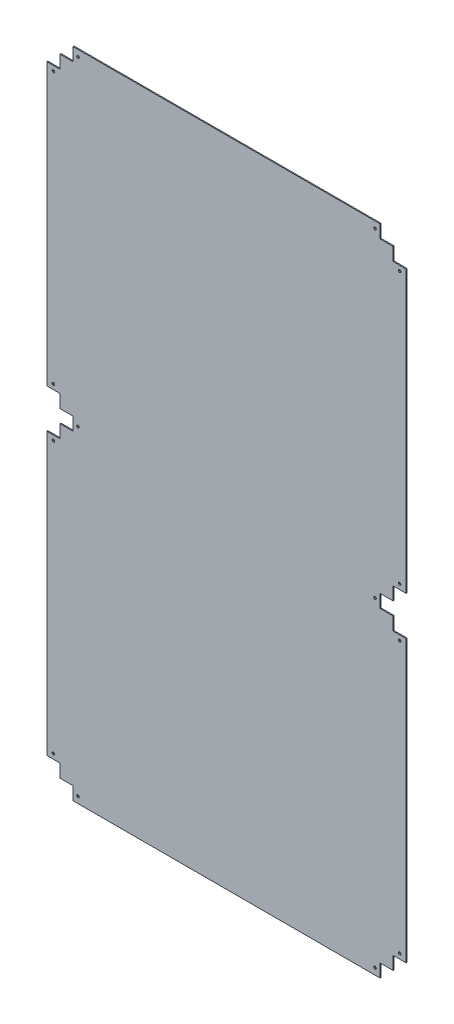
SolidWorks part; units mm, degrees
ref_plane "Piano frontale" through (0, 0, 0) normal (0, 0, 1) x (1, 0, 0)
ref_plane "Piano superiore" through (0, 0, 0) normal (0, 1, 0) x (1, 0, 0)
ref_plane "Piano destro" through (0, 0, 0) normal (1, 0, 0) x (0, 0, -1)
sketch "Schizzo1" plane through (0, 0, 0) normal (0, 0, 1) x (1, 0, 0)
  line L1 (-550, 1000) -> (550, 1000)
  line L2 (-550, 1000) -> (-550, -1000)
  line L3 (-550, -1000) -> (550, -1000)
  line L4 (550, 1000) -> (550, -1000)
  line L5 (-550, 1000) -> (550, -1000) construction
  line L6 (-550, -1000) -> (550, 1000) construction
  point P0 (0, 0)
  dimension "D1" = 2000
  dimension "D2" = 1100
base flange "Base-Flangia1" sketch "Schizzo1" thickness 3 reverse thickness direction no parameters "D1"=1
sketch "Schizzo2" plane through (0, 0, 0) normal (0, 0, 1) x (1, 0, 0)
  line L0 (-550, -1000) -> (-470, -1000)
  line L33 (-550, -1000) -> (550, -1000) construction
  line L34 (-470, -1000) -> (-470, -960)
  line L35 (-470, -960) -> (-510, -960)
  line L36 (-510, -960) -> (-510, -920)
  line L37 (-510, -920) -> (-550, -920)
  line L38 (-550, 1000) -> (-550, -1000) construction
  line L39 (-550, -920) -> (-550, -1000)
  line L40 (550, -1000) -> (470, -1000)
  line L41 (470, -1000) -> (470, -960)
  line L42 (470, -960) -> (510, -960)
  line L43 (510, -960) -> (510, -920)
  line L44 (510, -920) -> (550, -920)
  line L45 (550, 1000) -> (550, -1000) construction
  line L46 (550, -920) -> (550, -1000)
  line L47 (550, 1000) -> (470, 1000)
  line L48 (-550, 1000) -> (550, 1000) construction
  line L49 (470, 1000) -> (470, 960)
  line L50 (470, 960) -> (510, 960)
  line L51 (510, 960) -> (510, 920)
  line L52 (510, 920) -> (550, 920)
  line L53 (550, 920) -> (550, 1000)
  line L54 (-550, 1000) -> (-550, 920)
  line L55 (-550, 920) -> (-510, 920)
  line L56 (-510, 920) -> (-510, 960)
  line L57 (-510, 960) -> (-470, 960)
  line L58 (-470, 960) -> (-470, 1000)
  line L59 (-470, 1000) -> (-550, 1000)
  dimension "D1" = 80
  dimension "D2" = 80
  dimension "D3" = 40
  dimension "D4" = 40
  dimension "D5" = 40
  dimension "D6" = 80
  dimension "D7" = 80
  dimension "D8" = 40
  dimension "D9" = 40
  dimension "D10" = 40
  dimension "D11" = 80
  dimension "D12" = 80
  dimension "D13" = 80
  dimension "D14" = 80
  dimension "D15" = 40
  dimension "D16" = 40
extrude "Taglio-Estrusione1" cut sketch "Schizzo2" against normal through all normal cut yes
sketch "Schizzo4" plane through (0, 0, 0) normal (0, 0, 1) x (1, 0, 0)
  line L0 (-1000, 0) -> (49000, 0) construction
  line L1 (-550, -60) -> (-550, 60)
  line L2 (-550, 920) -> (-550, -920) construction
  line L3 (-550, 60) -> (-510, 60)
  line L4 (-510, 60) -> (-510, 20)
  line L5 (-510, 20) -> (-470, 20)
  line L6 (-470, 20) -> (-470, -20)
  line L7 (-510, -20) -> (-470, -20)
  line L8 (-510, -60) -> (-510, -20)
  line L9 (-550, -60) -> (-510, -60)
  line L10 (0, -1000) -> (0, 49000) construction
  line L11 (510, 20) -> (470, 20)
  line L12 (510, 60) -> (510, 20)
  line L13 (550, 60) -> (510, 60)
  line L14 (550, -60) -> (550, 60)
  line L15 (550, -60) -> (510, -60)
  line L16 (510, -60) -> (510, -20)
  line L17 (510, -20) -> (470, -20)
  line L18 (470, 20) -> (470, -20)
  point P12 (-470, 0)
  point P15 (-550, 0)
  dimension "D1" = 60
  dimension "D2" = 40
  dimension "D3" = 40
  dimension "D4" = 20
extrude "Taglio-Estrusione3" cut sketch "Schizzo4" against normal through all normal cut yes
sketch "Schizzo6" plane through (0, 0, -3) normal (0, 0, -1) x (-1, 0, 0)
  line L0 (0, -1000) -> (0, 49000) construction
  line L2 (470, 1000) -> (-470, 1000) construction
  line L4 (470, -20) -> (470, 20) construction
  line L6 (470, 20) -> (510, 20) construction
  line L7 (470, 960) -> (470, 1000) construction
  line L8 (550, 920) -> (550, 60) construction
  line L9 (550, 920) -> (510, 920) construction
  line L10 (550, -60) -> (510, -60) construction
  line L11 (550, -60) -> (550, -920) construction
  line L12 (510, 60) -> (550, 60) construction
  line L14 (510, -920) -> (550, -920) construction
  line L15 (470, -1000) -> (470, -960) construction
  line L16 (470, -1000) -> (-470, -1000) construction
  circle A1 centre (-454.75, -980) radius 4
  circle A2 centre (-530, -904.75) radius 4
  circle A3 centre (-530, -75.25) radius 4
  circle A4 centre (-454.75, 0) radius 4
  circle A5 centre (-530, 75.25) radius 4
  circle A6 centre (-530, 904.75) radius 4
  circle A7 centre (-454.75, 980) radius 4
  circle A56 centre (454.75, 980) radius 4
  circle A57 centre (530, 904.75) radius 4
  circle A58 centre (530, 75.25) radius 4
  circle A59 centre (454.75, 0) radius 4
  circle A60 centre (530, -75.25) radius 4
  circle A61 centre (530, -904.75) radius 4
  circle A62 centre (454.75, -980) radius 4
  dimension "D4" = 8
  dimension "D5" = 8
  dimension "D6" = 8
  dimension "D7" = 8
  dimension "D8" = 8
  dimension "D14" = 8
  dimension "D15" = 8
  dimension "D16" = 20
  dimension "D9" = 15.25
  dimension "D11" = 20
  dimension "D12" = 15.25
  dimension "D13" = 20
  dimension "D17" = 15.25
  dimension "D18" = 15.25
  dimension "D19" = 20
  dimension "D20" = 15.25
  dimension "D21" = 20
  dimension "D24" = 20
  dimension "D25" = 15.25
  dimension "D26" = 15.25
  dimension "D27" = 20
extrude "Taglio-Estrusione4" cut sketch "Schizzo6" against normal through all normal cut yes
sketch "Linee di piegatura1" [suppressed] plane through (0, 0, 0) normal (0, 1, 0) x (1, 0, 0)
sketch "Casella di contorno1" [suppressed] plane through (0, 0, 0) normal (0, 1, 0) x (1, 0, 0)
sheet metal parameters "Lamiera1" thickness 3 parameters "D1"=1
flat pattern "Ripetizione piatta1" [suppressed]
sketch "Linee di piegatura2" plane through (0, 0, 0) normal (0, 1, 0) x (1, 0, 0)
sketch3d "Casella di contorno2" [suppressed]
  line L0 (790, 1040, 0) -> (790, -1040, 0) construction
  line L1 (-790, 1040, 0) -> (-790, -1040, 0) construction
  line L2 (790, 1040, 0) -> (-790, 1040, 0) construction
  line L3 (790, -1040, 0) -> (-790, -1040, 0) construction
sheet metal parameters "Lamiera3" thickness 3 parameters "D1"=1
flat pattern "Ripetizione piatta1"
sketch "Linee di piegatura2" plane through (0, 0, 0) normal (0, 1, 0) x (1, 0, 0)
sketch3d "Casella di contorno2" [suppressed]
  line L0 (790, 1040, 0) -> (790, -1040, 0) construction
  line L1 (-790, 1040, 0) -> (-790, -1040, 0) construction
  line L2 (790, 1040, 0) -> (-790, 1040, 0) construction
  line L3 (790, -1040, 0) -> (-790, -1040, 0) construction
sheet metal parameters "Lamiera5" thickness 3 parameters "D1"=1
flat pattern "Ripetizione piatta1" [suppressed]
sketch "Linee di piegatura2" plane through (0, 0, 0) normal (0, 1, 0) x (1, 0, 0)
sketch3d "Casella di contorno2" [suppressed]
  line L0 (790, 1040, 0) -> (790, -1040, 0) construction
  line L1 (-790, 1040, 0) -> (-790, -1040, 0) construction
  line L2 (790, 1040, 0) -> (-790, 1040, 0) construction
  line L3 (790, -1040, 0) -> (-790, -1040, 0) construction
sketch "Schizzo3-1" [suppressed] plane through (0, 0, -3) normal (0, 0, -1) x (-1, 0, 0)
  arc A16 (774, -944.75) -> (766, -944.75) centre (770, -944.75) ccw
  arc A17 (766, -944.75) -> (774, -944.75) centre (770, -944.75) ccw
  arc A18 (694.75, -1024) -> (694.75, -1016) centre (694.75, -1020) ccw
  arc A19 (694.75, -1016) -> (694.75, -1024) centre (694.75, -1020) ccw
  arc A20 (-694.75, -1024) -> (-694.75, -1016) centre (-694.75, -1020) ccw
  arc A21 (-694.75, -1016) -> (-694.75, -1024) centre (-694.75, -1020) ccw
  arc A22 (-766, -944.75) -> (-774, -944.75) centre (-770, -944.75) ccw
  arc A23 (-774, -944.75) -> (-766, -944.75) centre (-770, -944.75) ccw
  arc A24 (766, 944.75) -> (774, 944.75) centre (770, 944.75) ccw
  arc A25 (774, 944.75) -> (766, 944.75) centre (770, 944.75) ccw
  arc A26 (694.75, 1016) -> (694.75, 1024) centre (694.75, 1020) ccw
  arc A27 (694.75, 1024) -> (694.75, 1016) centre (694.75, 1020) ccw
  arc A28 (-694.75, 1016) -> (-694.75, 1024) centre (-694.75, 1020) ccw
  arc A29 (-694.75, 1024) -> (-694.75, 1016) centre (-694.75, 1020) ccw
  arc A30 (-766, 944.75) -> (-774, 944.75) centre (-770, 944.75) ccw
  arc A31 (-774, 944.75) -> (-766, 944.75) centre (-770, 944.75) ccw
sheet metal parameters "Lamiera6" thickness 3 parameters "D1"=1
flat pattern "Ripetizione piatta1"
sketch "Linee di piegatura2" plane through (0, 0, 0) normal (0, 1, 0) x (1, 0, 0)
sketch3d "Casella di contorno2" [suppressed]
  line L0 (550, 1000, 0) -> (550, -1000, 0) construction
  line L1 (-550, 1000, 0) -> (-550, -1000, 0) construction
  line L2 (550, 1000, 0) -> (-550, 1000, 0) construction
  line L3 (550, -1000, 0) -> (-550, -1000, 0) construction
